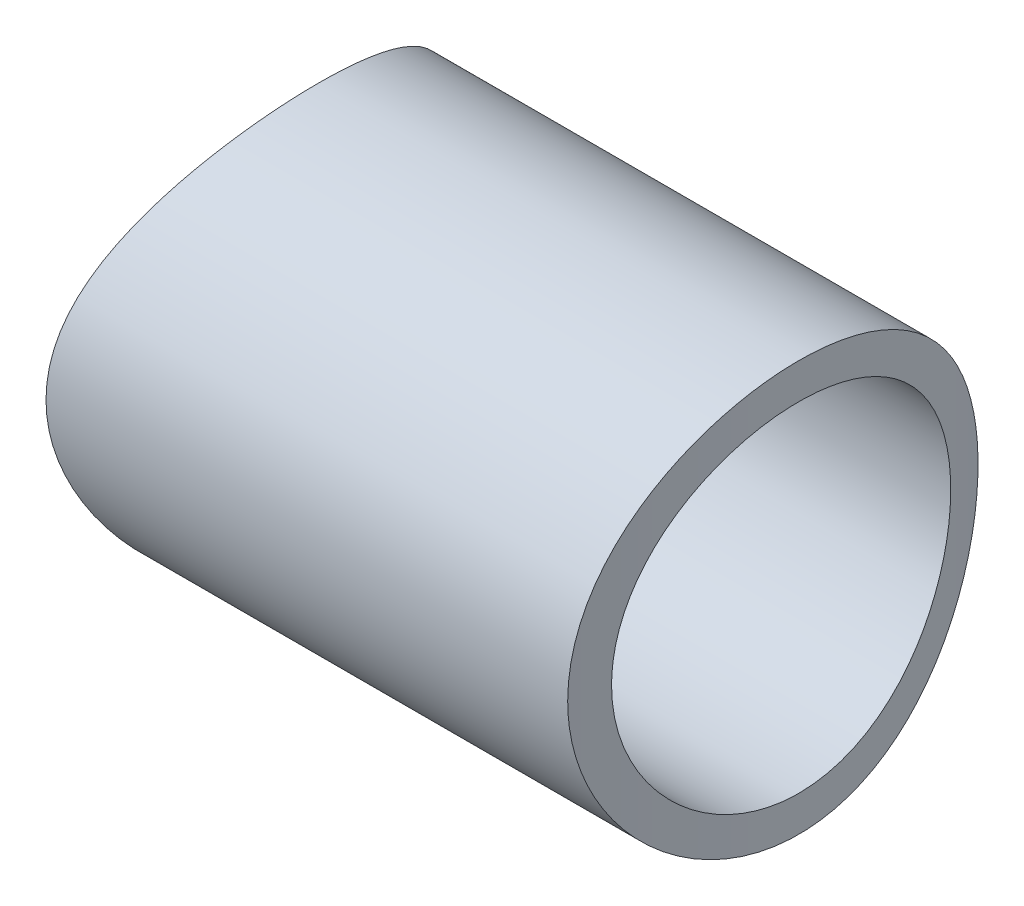
SolidWorks part; units mm, degrees
material "PTFE (general)"
ref_plane "Front Plane" through (0, 0, 0) normal (0, 0, 1) x (1, 0, 0)
ref_plane "Top Plane" through (0, 0, 0) normal (0, 1, 0) x (1, 0, 0)
ref_plane "Right Plane" through (0, 0, 0) normal (1, 0, 0) x (0, 0, -1)
sketch "Sketch1" plane through (0, 0, 0) normal (0, 1, 0) x (1, 0, 0)
  circle A0 centre (0, 0) radius 46.53
  circle A1 centre (0, 0) radius 19.53
  dimension "D1" = 39.06
  dimension "D2" = 93.06
extrude "Boss-Extrude1" add sketch "Sketch1" along normal blind 1
sketch "Sketch2" plane through (0, 1, 0) normal (0, 1, 0) x (1, 0, 0)
  circle A0 centre (0, 0) radius 20.53
  circle A1 centre (0, 0) radius 19.53
  circle A2 centre (0, 0) radius 46.53
  circle A3 centre (0, 0) radius 45.53
  circle A4 centre (0, 0) radius 19.53 construction
  circle A5 centre (0, 0) radius 46.53 construction
  dimension "D1" = 0
  dimension "D2" = 1
  dimension "D3" = 0
  dimension "D4" = 1
extrude "Boss-Extrude2" add sketch "Sketch2" along normal blind 25 contours A2 | A1 | A0 | A3
sketch "Sketch3" plane through (0, 0, 0) normal (1, 0, 0) x (0, 0, -1)
  line L1 (-46.53, 0) -> (46.53, 0) construction
  circle A1 centre (0, 11) radius 9.53
  dimension "D1" = 11
  dimension "D2" = 19.06
extrude "Cut-Extrude1" cut sketch "Sketch3" along normal through all
sketch "Sketch9" plane through (0, 0, 0) normal (1, 0, 0) x (0, 0, -1)
  circle A0 centre (0, 11) radius 11.53
  circle A1 centre (0, 11) radius 9.53
  dimension "D1" = 2
  dimension "D2" = 19.06
extrude "Boss-Extrude3" add sketch "Sketch9" along normal up to surface (45.0788 mm away) up to face at (0, 0, 46.53)
sketch "Sketch10" plane through (0, 26, 0) normal (0, 1, 0) x (1, 0, 0)
  line L5 (0, 11.53) -> (0, -11.53) construction
  line L10 (1.9221, 19.4352) -> (43.95, 15.2786)
  line L11 (1.9221, -19.4352) -> (43.95, -15.2786)
  circle A3 centre (0, 0) radius 19.53 construction
  circle A4 centre (0, 0) radius 19.53
  circle A5 centre (0, 0) radius 46.53
  circle A6 centre (0, 0) radius 46.53 construction
  circle M1 centre (0, 0) radius 20.53
  circle M2 centre (0, 0) radius 19.53
  dimension "D2" = 0
  dimension "D1" = 0
extrude "Cut-Extrude2" cut sketch "Sketch10" against normal through all both and the other way through all contours M2 | L11 L10 M2 M1 | L10 A5 L11 M1 | A4 region at (-20.0313, 26, 0) region at (0, 26, 0) region at (-21.828, 26, 0)
sketch "Sketch11" plane through (0, 0, 0) normal (1, 0, 0) x (0, 0, -1)
  circle A0 centre (0, 11) radius 11.53
  circle A1 centre (0, 11) radius 9.53 construction
  circle A2 centre (0, 11) radius 50
  dimension "D1" = 2
  dimension "D2" = 100
extrude "Cut-Extrude4" cut sketch "Sketch11" along normal through all both and the other way through all
